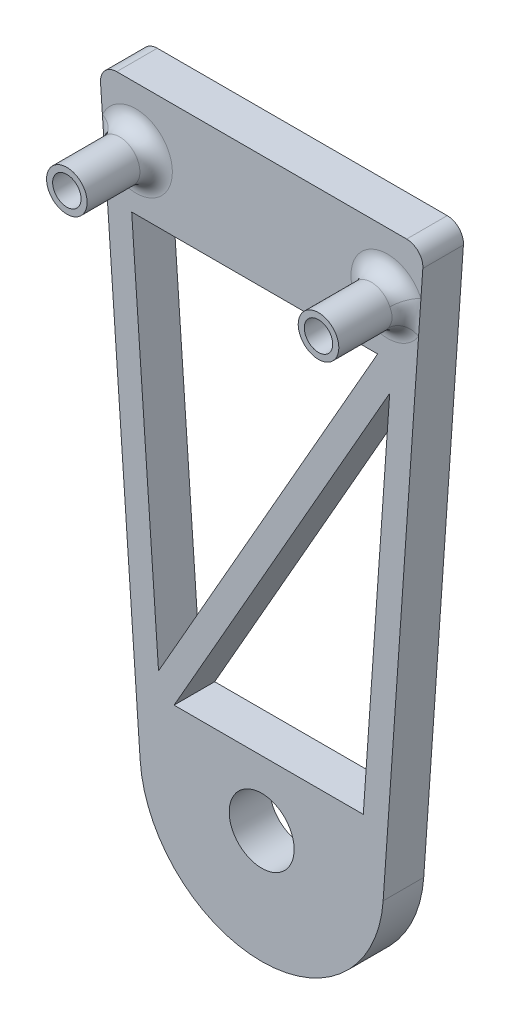
SolidWorks part; units mm, degrees
material "PLA"
ref_plane "Alzado" through (0, 0, 0) normal (0, 0, 1) x (1, 0, 0)
ref_plane "Planta" through (0, 0, 0) normal (0, 1, 0) x (1, 0, 0)
ref_plane "Vista lateral" through (0, 0, 0) normal (1, 0, 0) x (0, 0, -1)
sketch "Croquis1" plane through (0, 0, 0) normal (0, 0, 1) x (1, 0, 0)
  line L0 (0, 0) -> (0, -128.0927) construction
  line L1 (-20.0014, 0) -> (20.0014, 0)
  line L2 (20.0014, 0) -> (14.9635, -72.0463)
  line L3 (-20.0014, 0) -> (-14.9635, -72.0463)
  line L4 (-16.0119, -14.0463) -> (16.0119, -14.0463)
  line L5 (16.0119, -14.0463) -> (12.5155, -64.0463)
  line L6 (12.5155, -64.0463) -> (-12.5155, -64.0463)
  line L7 (-12.5155, -64.0463) -> (-16.0119, -14.0463)
  line L8 (-14.9635, -72.0463) -> (14.9635, -72.0463) construction
  line L9 (-12.7041, -61.35) -> (14.2849, -14.0463)
  line L10 (-12.5155, -64.0463) -> (16.0119, -14.0463) construction
  line L11 (-10.7886, -64.0463) -> (15.7707, -17.496)
  arc A0 (14.9635, -72.0463) -> (-14.9635, -72.0463) centre (0, -71) cw
  circle A1 centre (-15.5, -7.2763) radius 2.5
  circle A2 centre (15.5, -7.2763) radius 2.5
  circle A3 centre (-15.5, -7.2763) radius 1.75
  circle A4 centre (15.5, -7.2763) radius 1.75
  circle A5 centre (0, -72.0463) radius 4
  point P12 (0, -86)
  point P19 (0, -64.0463)
  dimension "D1" = 15
  dimension "D4" = 64.77
  dimension "D5" = 5
  dimension "D7" = 3.5
  dimension "D10" = 8
  dimension "D2" = 86
  dimension "D3" = 86
  dimension "D6" = 31
  dimension "D8" = 3
  dimension "D9" = 50
  dimension "D11" = 8
  dimension "D12" = 3
extrude "Saliente-Extruir1" add sketch "Croquis1" along normal mid plane 5 contours L0 L1 L3 A0 A1 | A1 | A2 | L1 L0 A0 L2 A2 | L6 L11 L5 L4 L9 L7 region at (0, -0.9485, 0) region at (1.6928, -39.1355, 0) region at (-17.9293, -7.2763, 0) region at (13.0707, -7.2763, 0)
extrude "Saliente-Extruir2" add sketch "Croquis1<3>" along normal blind 11 contours A1 | A2 | A3 | A4
sketch "Croquis1<3>" plane through (0, 0, 0) normal (0, 0, 1) x (1, 0, 0) same geometry as "Croquis1"
fillet "Redondeo1" radius 2 2 edges at (18, -7.2763, 2.5) (-13, -7.2763, 2.5)
fillet "Redondeo2" radius 2 2 edges at (20.0014, 0, 0) (-20.0014, 0, 0)
sketch "Croquis2" plane through (0, 0, -2.5) normal (0, 0, -1) x (-1, 0, 0)
  circle A12 centre (-15.5, -7.2763) radius 3
  circle A13 centre (15.5, -7.2763) radius 3
  dimension "D1" = 6
extrude "Cortar-Extruir1" cut sketch "Croquis2" against normal blind 2
